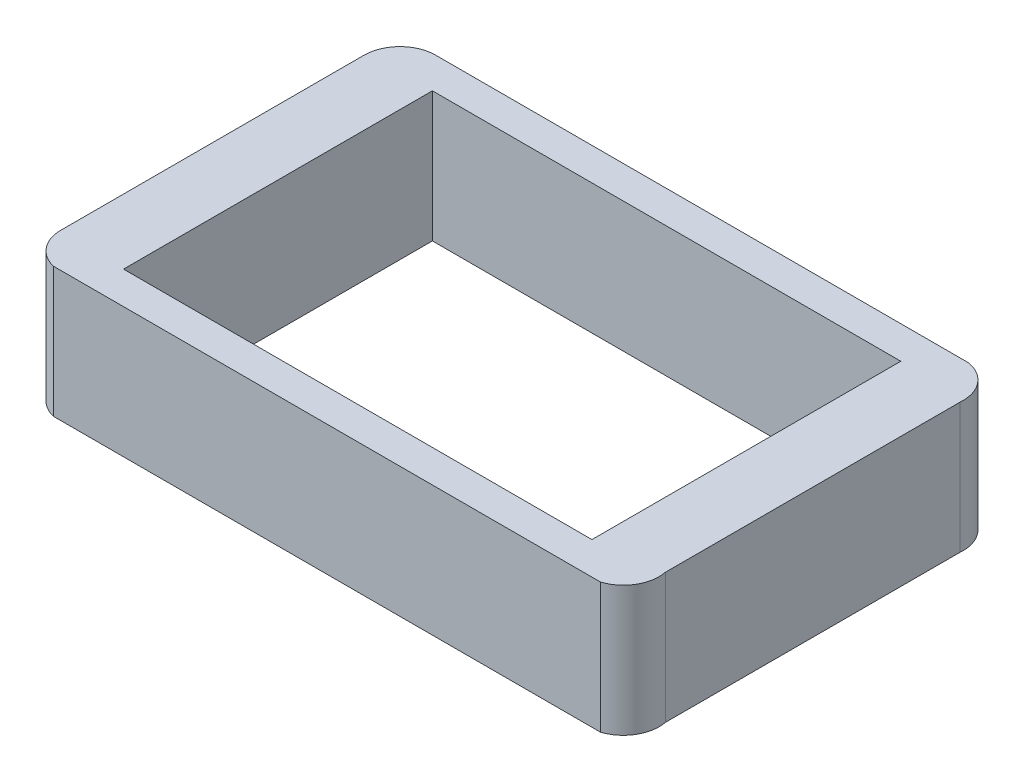
SolidWorks part; units mm, degrees
ref_plane "Front Plane" through (0, 0, 0) normal (0, 0, 1) x (1, 0, 0)
ref_plane "Top Plane" through (0, 0, 0) normal (0, 1, 0) x (1, 0, 0)
ref_plane "Right Plane" through (0, 0, 0) normal (1, 0, 0) x (0, 0, -1)
sketch "Sketch1" plane through (0, 0, 0) normal (0, 1, 0) x (1, 0, 0)
  line L1 (82.709, -55.6483) -> (-85.5571, -55.6483)
  line L2 (90.0634, -43.0733) -> (90.0634, 47.5439)
  line L3 (80.8648, 59.3517) -> (-82.9855, 59.3517)
  line L4 (-94.0139, -45.2987) -> (-94.0139, 48.3802)
  line L7 (70.0634, -45.6483) -> (-74.0139, -45.6483)
  line L8 (70.0634, -45.6483) -> (70.0634, 49.3517)
  line L9 (70.0634, 49.3517) -> (-74.0139, 49.3517)
  line L10 (-74.0139, -45.6483) -> (-74.0139, 49.3517)
  arc A0 (-94.0139, 48.3802) -> (-82.9855, 59.3517) centre (-83.0139, 48.3517) cw
  arc A1 (-94.0139, -45.2987) -> (-85.5571, -55.6483) centre (-83.0195, -44.945) ccw
  arc A2 (82.709, -55.6483) -> (90.0634, -43.0733) centre (79.2708, -45.1994) ccw
  arc A3 (80.8648, 59.3517) -> (90.0634, 47.5439) centre (79.1044, 48.4935) cw
  dimension "D3" = 20
  dimension "D4" = 10
  dimension "D5" = 20
  dimension "D1" = 115
  dimension "D2" = 10
extrude "Boss-Extrude1" add sketch "Sketch1" along normal blind 40
sketch "Sketch3" plane through (0, 40, 0) normal (0, 1, 0) x (1, 0, 0)
extrude "Boss-Extrude2" add sketch "Sketch1<2>" along normal blind 40
sketch "Sketch1<2>" plane through (0, 0, 0) normal (0, 1, 0) x (1, 0, 0) same geometry as "Sketch1"
